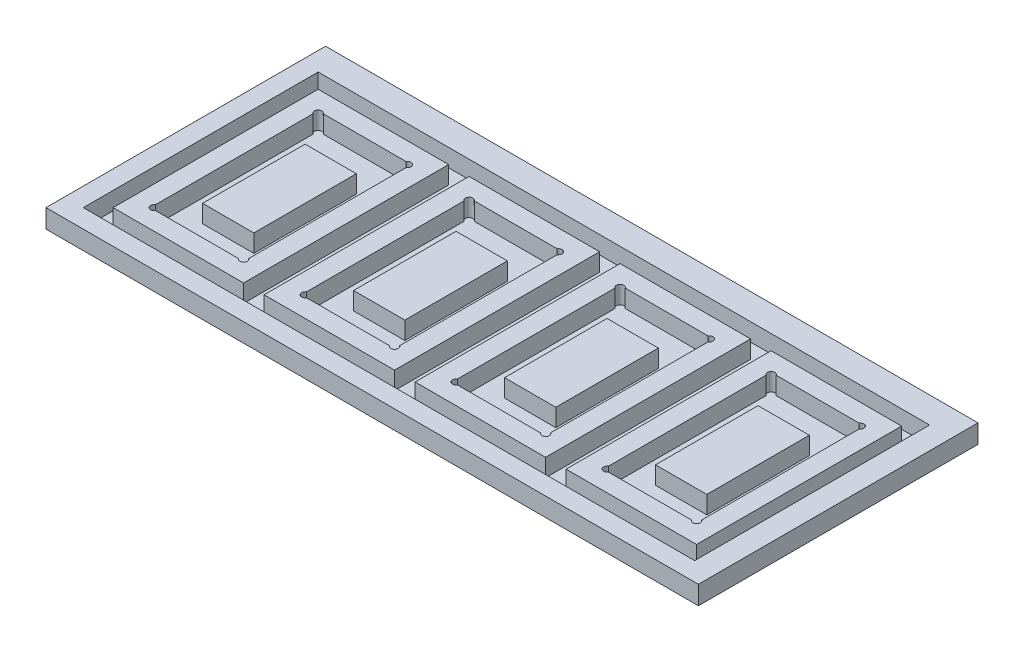
SolidWorks part; units mm, degrees
material "6061 Alloy"
ref_plane "Front Plane" through (0, 0, 0) normal (0, 0, 1) x (1, 0, 0)
ref_plane "Top Plane" through (0, 0, 0) normal (0, 1, 0) x (1, 0, 0)
ref_plane "Right Plane" through (0, 0, 0) normal (1, 0, 0) x (0, 0, -1)
sketch "Sketch1" plane through (0, 0, 0) normal (0, 1, 0) x (1, 0, 0)
  line L1 (-175, -75) -> (175, -75)
  line L2 (-175, -75) -> (-175, 75)
  line L3 (-175, 75) -> (175, 75)
  line L4 (175, -75) -> (175, 75)
  line L5 (-175, -75) -> (175, 75) construction
  line L6 (-175, 75) -> (175, -75) construction
  point P0 (0, 0)
  dimension "D1" = 350
  dimension "D2" = 150
extrude "Boss-Extrude1" add sketch "Sketch1" along normal blind 10
sketch "Sketch2" plane through (0, 10, 0) normal (0, 1, 0) x (1, 0, 0)
  line L0 (98.7562, 43) -> (143.2438, 43)
  line L1 (86, -57) -> (156, -57)
  line L2 (86, -57) -> (86, 53)
  line L3 (86, 53) -> (156, 53)
  line L4 (156, -57) -> (156, 53)
  line L5 (86, -57) -> (156, 53) construction
  line L6 (86, 53) -> (156, -57) construction
  line L7 (146, -44.2438) -> (146, 40.2438)
  line L8 (98.7562, -47) -> (143.2438, -47)
  line L9 (96, -44.2438) -> (96, 40.2438)
  line L10 (96, 43) -> (146, 43) construction
  line L11 (96, -47) -> (96, 43) construction
  line L12 (146, -47) -> (146, 43) construction
  line L13 (96, -47) -> (146, -47) construction
  line L14 (-175, -75) -> (175, -75) construction
  line L15 (108, 24) -> (135.5, 24)
  line L16 (108, 24) -> (108, -31)
  line L17 (108, -31) -> (135.5, -31)
  line L18 (135.5, 24) -> (135.5, -31)
  line L24 (96, -47) -> (96, -44.2438) construction
  line L25 (96, -47) -> (98.7562, -47) construction
  line L26 (143.2438, -47) -> (146, -47) construction
  line L27 (146, -47) -> (146, -44.2438) construction
  line L28 (96, 43) -> (97.0607, 41.9393) construction
  line L29 (146, 43) -> (146, 40.2438) construction
  line L30 (96, 43) -> (98.7562, 43) construction
  line L31 (96, 43) -> (96, 40.2438) construction
  line L32 (146, 43) -> (144.9393, 41.9393) construction
  line L33 (146, -47) -> (144.9393, -45.9393) construction
  line L34 (96, -47) -> (97.0607, -45.9393) construction
  line L35 (5, 53) -> (75, 53)
  line L36 (17.7562, 43) -> (62.2438, 43)
  line L37 (75, -57) -> (75, 53)
  line L38 (65, -44.2438) -> (65, 40.2438)
  line L39 (15, -44.2438) -> (15, 40.2438)
  line L40 (5, -57) -> (5, 53)
  line L41 (5, -57) -> (75, -57)
  line L42 (17.7562, -47) -> (62.2438, -47)
  line L43 (27, 24) -> (27, -31)
  line L44 (27, -31) -> (54.5, -31)
  line L45 (54.5, 24) -> (54.5, -31)
  line L46 (27, 24) -> (54.5, 24)
  line L47 (-76, 53) -> (-6, 53)
  line L48 (-63.2438, 43) -> (-18.7562, 43)
  line L49 (-6, -57) -> (-6, 53)
  line L50 (-16, -44.2438) -> (-16, 40.2438)
  line L51 (-66, -44.2438) -> (-66, 40.2438)
  line L52 (-76, -57) -> (-76, 53)
  line L53 (-76, -57) -> (-6, -57)
  line L54 (-63.2438, -47) -> (-18.7562, -47)
  line L55 (-54, 24) -> (-54, -31)
  line L56 (-54, -31) -> (-26.5, -31)
  line L57 (-26.5, 24) -> (-26.5, -31)
  line L58 (-54, 24) -> (-26.5, 24)
  line L59 (-157, 53) -> (-87, 53)
  line L60 (-144.2438, 43) -> (-99.7562, 43)
  line L61 (-87, -57) -> (-87, 53)
  line L62 (-97, -44.2438) -> (-97, 40.2438)
  line L63 (-147, -44.2438) -> (-147, 40.2438)
  line L64 (-157, -57) -> (-157, 53)
  line L65 (-157, -57) -> (-87, -57)
  line L66 (-144.2438, -47) -> (-99.7562, -47)
  line L67 (-135, 24) -> (-135, -31)
  line L68 (-135, -31) -> (-107.5, -31)
  line L69 (-107.5, 24) -> (-107.5, -31)
  line L70 (-135, 24) -> (-107.5, 24)
  line L73 (-175, 75) -> (-175, -75) construction
  line L79 (-165, 61) -> (163, 61)
  line L80 (-165, 61) -> (-165, -65)
  line L81 (-165, -65) -> (163, -65)
  line L82 (163, 61) -> (163, -65)
  arc A4 (146, 40.2438) -> (143.2438, 43) centre (144.9393, 41.9393) ccw
  arc A5 (98.7562, 43) -> (96, 40.2438) centre (97.0607, 41.9393) ccw
  arc A6 (96, -44.2438) -> (98.7562, -47) centre (97.0607, -45.9393) ccw
  arc A7 (143.2438, -47) -> (146, -44.2438) centre (144.9393, -45.9393) ccw
  arc A8 (65, 40.2438) -> (62.2438, 43) centre (63.9393, 41.9393) ccw
  arc A9 (17.7562, 43) -> (15, 40.2438) centre (16.0607, 41.9393) ccw
  arc A10 (62.2438, -47) -> (65, -44.2438) centre (63.9393, -45.9393) ccw
  arc A11 (15, -44.2438) -> (17.7562, -47) centre (16.0607, -45.9393) ccw
  arc A12 (-16, 40.2438) -> (-18.7562, 43) centre (-17.0607, 41.9393) ccw
  arc A13 (-63.2438, 43) -> (-66, 40.2438) centre (-64.9393, 41.9393) ccw
  arc A14 (-18.7562, -47) -> (-16, -44.2438) centre (-17.0607, -45.9393) ccw
  arc A15 (-66, -44.2438) -> (-63.2438, -47) centre (-64.9393, -45.9393) ccw
  arc A16 (-97, 40.2438) -> (-99.7562, 43) centre (-98.0607, 41.9393) ccw
  arc A17 (-144.2438, 43) -> (-147, 40.2438) centre (-145.9393, 41.9393) ccw
  arc A18 (-99.7562, -47) -> (-97, -44.2438) centre (-98.0607, -45.9393) ccw
  arc A19 (-147, -44.2438) -> (-144.2438, -47) centre (-145.9393, -45.9393) ccw
  dimension "D3" = 4
  dimension "D13" = 45
  dimension "D17" = 4
  dimension "D22" = 4
  dimension "D23" = 4
  dimension "D1" = 110
  dimension "D4" = 55
  dimension "D5" = 27.5
  dimension "D6" = 8
  dimension "D7" = 12
  dimension "D8" = 7
  dimension "D9" = 19
  dimension "D10" = 70
  dimension "D11" = 16
  dimension "D12" = 10.5
  dimension "D14" = 1.5
  dimension "D15" = 45
  dimension "D16" = 1.5
  dimension "D18" = 1.5
  dimension "D19" = 45
  dimension "D20" = 1.5
  dimension "D21" = 45
  dimension "D25" = 11
  dimension "D26" = 10
  dimension "D27" = 8
  dimension "D28" = 8
  dimension "D29" = 10
  dimension "D2" = 10
  dimension "D24" = 4
extrude "Cut-Extrude1" cut sketch "Sketch2" against normal blind 9.5 contours L82 L79 L80 L81 L65 L64 L59 L61 L53 L52 L47 L49 L41 L40 L35 L37 L4 L1 L2 L3 | L63 A19 L66 A18 L62 A16 L60 A17 L67 L70 L69 L68 | L51 A15 L54 A14 L50 A12 L48 A13 L55 L58 L57 L56 | L39 A11 L42 A10 L38 A8 L36 A9 L43 L46 L45 L44 | L8 A7 L7 A4 L0 A5 L9 A6 L15 L18 L17 L16 region at (121, 10, -41.9449) region at (40, 10, -41.9449) region at (-41, 10, -41.9449) region at (-122, 10, -41.9449) region at (-2.4628, 10, 2)
sketch "Sketch3" plane through (0, 10, 0) normal (0, 1, 0) x (1, 0, 0)
  line L0 (175, 75) -> (-175, 75) construction
  line L1 (-131, 75) -> (-112, 75)
  line L2 (-131, 75) -> (-131, -75)
  line L3 (-131, -75) -> (-112, -75)
  line L4 (-112, 75) -> (-112, -75)
  line L5 (-175, -75) -> (175, -75) construction
  line L6 (-122, 43) -> (-122, -47) construction
  line L7 (-144.2438, 43) -> (-99.7562, 43) construction
  line L8 (-144.2438, -47) -> (-99.7562, -47) construction
  line L9 (-144.2438, -47) -> (-99.7562, -47) construction
  dimension "D1" = 10
  dimension "D2" = 9
sketch "Sketch4" plane through (0, 10, 0) normal (0, 1, 0) x (1, 0, 0)
  line L0 (-147, -2) -> (-97, -2) construction
  line L1 (-175, 18) -> (-87, 18)
  line L2 (-175, 18) -> (-175, -22)
  line L3 (-175, -22) -> (-87, -22)
  line L4 (-87, 18) -> (-87, -22)
  line L5 (-147, -44.2438) -> (-147, 40.2438) construction
  line L6 (-97, -44.2438) -> (-97, 40.2438) construction
  line L7 (-175, 75) -> (-175, -75) construction
  line L8 (-87, -57) -> (-87, 53) construction
  dimension "D1" = 20
  dimension "D2" = 20
